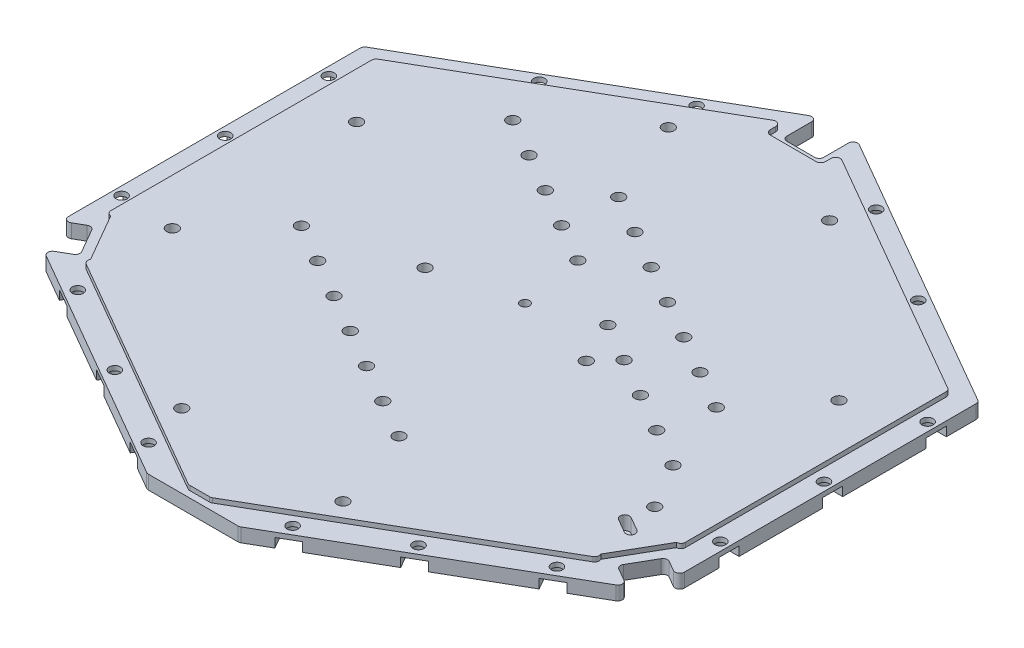
SolidWorks part; units mm, degrees
material "Copper"
ref_plane "Front Plane" through (0, 0, 0) normal (0, 0, 1) x (1, 0, 0)
ref_plane "Top Plane" through (0, 0, 0) normal (0, 1, 0) x (1, 0, 0)
ref_plane "Right Plane" through (0, 0, 0) normal (1, 0, 0) x (0, 0, -1)
sketch "Sketch1" plane through (0, 0, 0) normal (0, 1, 0) x (1, 0, 0)
  line L1 (-67.3538, -38.8868) -> (0, -77.7735)
  line L2 (0, -77.7735) -> (67.3538, -38.8868)
  line L3 (67.3538, -38.8868) -> (67.3538, 38.8868)
  line L4 (67.3538, 38.8868) -> (0, 77.7735)
  line L5 (0, 77.7735) -> (-67.3538, 38.8868)
  line L6 (-67.3538, 38.8868) -> (-67.3538, -38.8868)
  line L7 (-62.3538, -36) -> (0, -72) construction
  line L8 (0, -72) -> (62.3538, -36) construction
  line L9 (62.3538, -36) -> (62.3538, 36) construction
  line L10 (62.3538, 36) -> (0, 72) construction
  line L11 (0, 72) -> (-62.3538, 36) construction
  line L12 (-62.3538, 36) -> (-62.3538, -36) construction
  circle A0 centre (0, 0) radius 67.3538 construction
  circle A1 centre (0, 0) radius 62.3538 construction
  dimension "D1" = 5
  dimension "D2" = 72
extrude "Boss-Extrude1" add sketch "Sketch1" along normal blind 4
sketch "Sketch2" plane through (0, 4, 0) normal (0, 1, 0) x (1, 0, 0)
  line L0 (-67.3538, 38.8868) -> (-67.3538, 31.9585)
  line L1 (-67.3538, 38.8868) -> (-67.3538, -38.8868) construction
  line L2 (-67.3538, 31.9585) -> (0, 70.8453)
  line L3 (0, 70.8453) -> (67.3538, 31.9585)
  line L4 (67.3538, -38.8868) -> (67.3538, 38.8868) construction
  line L5 (67.3538, 31.9585) -> (67.3538, 38.8868)
  line L6 (67.3538, 38.8868) -> (0, 77.7735)
  line L7 (0, 77.7735) -> (-67.3538, 38.8868)
  line L8 (0, 77.7735) -> (-67.3538, 38.8868) construction
  dimension "D1" = 6
extrude "Cut-Extrude1" cut sketch "Sketch2" against normal up to next
sketch "Sketch4" plane through (0, 4, 0) normal (0, 1, 0) x (1, 0, 0)
  line L0 (-67.3538, 31.9585) -> (-67.3538, -38.8868)
  line L1 (-67.3538, 31.9585) -> (-67.3538, -38.8868) construction
  line L2 (-67.3538, -38.8868) -> (0, -77.7735)
  line L3 (0, -77.7735) -> (67.3538, -38.8868)
  line L4 (67.3538, -38.8868) -> (67.3538, 31.9585)
  line L7 (62.3538, 29.6491) -> (62.3538, -36)
  line L8 (62.3538, -36) -> (0, -72)
  line L9 (0, -72) -> (-62.3538, -36)
  line L10 (-62.3538, -36) -> (-62.3538, 29.6491)
  line L30 (-67.3538, 31.9585) -> (0, 70.8453)
  line L39 (0, 70.8453) -> (67.3538, 31.9585)
  line L40 (-62.3538, 29.6491) -> (0, 65.6491)
  line L41 (0, 65.6491) -> (62.3538, 29.6491)
  dimension "D1" = 5
  dimension "D2" = 5
  dimension "D3" = 5
  dimension "D4" = 4.5
extrude "Cut-Extrude3" cut sketch "Sketch4" against normal blind 1
sketch "Sketch8" plane through (0, 4, 0) normal (0, 1, 0) x (1, 0, 0)
  line L0 (54.3431, -31.375) -> (51.312, -29.625) construction
  line L1 (53.8431, -32.241) -> (50.812, -30.491)
  line L2 (54.8431, -30.509) -> (51.812, -28.759)
  line L4 (-62.3538, 36) -> (62.3538, -36) construction
  line L7 (62.3538, 29.6491) -> (0, 65.6491) construction
  line L8 (0, 72) -> (0, -72) construction
  circle A0 centre (0, 0) radius 1
  arc A2 (53.8431, -32.241) -> (54.8431, -30.509) centre (54.3431, -31.375) ccw
  arc A3 (51.812, -28.759) -> (50.812, -30.491) centre (51.312, -29.625) ccw
  point P6 (52.8275, -30.5)
  dimension "D1" = 2
  dimension "D2" = 1
  dimension "D3" = 3.5
  dimension "D4" = 61
extrude "Cut-Extrude5" cut sketch "Sketch8" against normal offset from surface (3 mm away) 1 up to face at (0, 0, 3.4641)
sketch "Sketch5" plane through (0, 0, 0) normal (0, -1, 0) x (1, 0, 0)
  line L0 (0, 77.7735) -> (10, 72)
  line L1 (0, 77.7735) -> (67.3538, 38.8868) construction
  line L2 (10, 72) -> (-10, 72)
  line L3 (-67.3538, 38.8868) -> (0, 77.7735) construction
  line L4 (-10, 72) -> (0, 77.7735)
  line L5 (-4, -68.5359) -> (-4, -59.8859)
  line L6 (0, -70.8453) -> (0, -59.8859) construction
  line L7 (-4, -59.8859) -> (4, -59.8859)
  line L8 (4, -59.8859) -> (4, -68.5359)
  line L9 (67.3538, 38.8868) -> (63.3538, 41.1962)
  line L10 (4, -68.5359) -> (0, -70.8453)
  line L11 (0, -70.8453) -> (-4, -68.5359)
  line L12 (0, 77.7735) -> (67.3538, 38.8868) construction
  line L13 (63.3538, 41.1962) -> (58.3049, 38.2812)
  line L14 (58.3049, 38.2812) -> (62.3049, 31.3529)
  line L15 (0, -70.8453) -> (-67.3538, -31.9585) construction
  line L16 (67.3538, -31.9585) -> (0, -70.8453) construction
  line L17 (62.3049, 31.3529) -> (67.3538, 34.2679)
  line L18 (67.3538, 38.8868) -> (67.3538, -31.9585) construction
  line L19 (67.3538, 34.2679) -> (67.3538, 38.8868)
  line L20 (-67.3538, 38.8868) -> (-67.3538, 34.2679)
  line L21 (-67.3538, -31.9585) -> (-67.3538, 38.8868) construction
  line L22 (-67.3538, 34.2679) -> (-62.3049, 31.3529)
  line L23 (-62.3049, 31.3529) -> (-58.3049, 38.2812)
  line L24 (-58.3049, 38.2812) -> (-63.3538, 41.1962)
  line L25 (-67.3538, 38.8868) -> (0, 77.7735) construction
  line L26 (-63.3538, 41.1962) -> (-67.3538, 38.8868)
  point P5 (0, 72)
  dimension "D1" = 8.65
  dimension "D2" = 8
  dimension "D3" = 120
  dimension "D4" = 5.83
  dimension "D5" = 5.83
  dimension "D6" = 8
  dimension "D7" = 8
  dimension "D8" = 4
  dimension "D9" = 4
extrude "Cut-Extrude4" cut sketch "Sketch5" against normal up to surface (3 mm away) up to face at (0, 3, 3.1754)
sketch "Sketch16" plane through (0, 0, 0) normal (0, -1, 0) x (1, 0, 0)
  line L0 (67.3538, 38.8868) -> (66.8538, 39.1754)
  line L2 (-66.8538, -31.6699) -> (-66.8538, 39.1754)
  line L4 (67.3538, -31.9585) -> (67.3538, 38.8868)
  line L5 (67.3538, 38.8868) -> (67.3538, -38.8868) construction
  line L6 (0, 77.7735) -> (67.3538, 38.8868) construction
  line L7 (-67.3538, 38.8868) -> (-66.8538, 39.1754)
  line L9 (66.8538, -31.6699) -> (66.8538, 39.1754)
  line L11 (-67.3538, -31.9585) -> (-67.3538, 38.8868)
  line L12 (-67.3538, 38.8868) -> (0, 77.7735) construction
  line L13 (-67.3538, -38.8868) -> (-67.3538, 38.8868) construction
  line L15 (66.8538, -31.6699) -> (0, -70.2679)
  line L16 (0, -70.2679) -> (-66.8538, -31.6699)
  line L18 (-67.3538, -31.9585) -> (0, -70.8453)
  line L20 (0, -70.8453) -> (67.3538, -31.9585)
  line L22 (67.3538, -31.9585) -> (4, -68.5359) construction
  line L23 (-4, -68.5359) -> (-67.3538, -31.9585) construction
  line L24 (67.3538, 34.2679) -> (67.3538, -31.9585) construction
  dimension "D1" = 0.5
  dimension "D2" = 0.5
  dimension "D3" = 0.5
  dimension "D4" = 0.5
extrude "Cut-Extrude7" cut sketch "Sketch16" against normal through all
hole_wizard "Tap Drill for M3x0.5 Tap1" positions "Sketch9" profile "Sketch10" hole size "M3x0.5" standard "ANSI Metric" end condition through all
sketch "Sketch9" plane through (0, 4, 0) normal (0, 1, 0) x (1, 0, 0)
  line L0 (-5.9392, -68.571) -> (11.3328, -38.655) construction
  line L2 (-58.3538, -38.3094) -> (0, -72) construction
  line L3 (-62.3538, -36) -> (0, -72) construction
  line L4 (-51.8644, 5.1642) -> (-35.7354, 33.1005) construction
  line L5 (-51.8644, 5.1642) -> (-18.4289, -14.1398) construction
  line L6 (-35.7354, 33.1005) -> (-2.2999, 13.7965) construction
  line L7 (-18.4289, -14.1398) -> (-2.2999, 13.7965) construction
  line L8 (-3.0309, -23.0298) -> (13.0981, 4.9065) construction
  line L9 (-3.0309, -23.0298) -> (30.4046, -42.3338) construction
  line L10 (13.0981, 4.9065) -> (46.5336, -14.3975) construction
  line L11 (30.4046, -42.3338) -> (46.5336, -14.3975) construction
  line L12 (-18.9587, 30.7468) -> (-16.9267, 34.2663) construction
  line L13 (-18.9587, 30.7468) -> (38.3216, -2.324) construction
  line L14 (-16.9267, 34.2663) -> (40.3536, 1.1956) construction
  line L15 (38.3216, -2.324) -> (40.3536, 1.1956) construction
  point P0 (11.3328, -38.655)
  point P1 (46.5336, -14.3975)
  point P3 (40.3536, 1.1956)
  point P411 (2.9739, -33.829)
  point P412 (-5.385, -29.003)
  point P413 (-13.7438, -24.177)
  point P414 (-22.1027, -19.351)
  point P415 (-30.4616, -14.525)
  point P416 (-38.8205, -9.699)
  point P431 (38.1747, -9.5715)
  point P432 (29.8158, -4.7455)
  point P433 (21.4569, 0.0805)
  point P434 (13.0981, 4.9065)
  point P437 (-2.2999, 13.7965)
  point P443 (-10.6588, 18.6225)
  point P444 (-19.0176, 23.4485)
  point P445 (-27.3765, 28.2745)
  point P446 (-35.7354, 33.1005)
  point P454 (31.9947, 6.0216)
  point P455 (23.6358, 10.8476)
  point P456 (15.2769, 15.6736)
  point P457 (6.9181, 20.4996)
  point P458 (-1.4408, 25.3256)
  point P459 (-9.7997, 30.1516)
  dimension "D1" = 34.544
  dimension "D2" = 6.858
  dimension "D3" = 7
  dimension "D4" = 32.258
  dimension "D5" = 4.064
  dimension "D6" = 32.258
  dimension "D7" = 6.35
  dimension "D8" = 6.35
  dimension "D11" = 4.826
  dimension "D12" = 7
  dimension "D13" = 8.89
  dimension "D14" = 8.89
  dimension "D9" = 5
  dimension "D10" = 5
sketch "Sketch10" plane through (11.3328, 4, 38.655) normal (1, 0, 0) x (0, 0, 1)
  line L0 (0, 0) -> (0, 4)
  line L1 (0, 4) -> (1.25, 4)
  line L2 (1.25, 4) -> (1.25, 0)
  line L5 (1.25, 0) -> (0, 0)
  line L11 (0, -6.35) -> (0, 107.95) construction
  dimension "Thru Hole Dia." = 2.5
  dimension "Thru Hole Depth" = 4
hole_wizard "Tap Drill for M3x0.5 Tap2" positions "Sketch11" profile "Sketch12" hole size "M3x0.5" standard "ANSI Metric" end condition through all
sketch "Sketch11" plane through (0, 0, 0) normal (0, -1, 0) x (-1, 0, 0)
  line L3 (17.5, -57) -> (-17.5, -57) construction
  line L4 (17.5, -57) -> (17.5, 48.637) construction
  line L5 (17.5, 48.637) -> (-17.5, 48.637) construction
  line L6 (-17.5, -57) -> (-17.5, 48.637) construction
  line L8 (52.3538, -24.1815) -> (-52.3538, -24.1815) construction
  line L9 (52.3538, -24.1815) -> (52.3538, 15.8185) construction
  line L10 (52.3538, 15.8185) -> (-52.3538, 15.8185) construction
  line L11 (-52.3538, -24.1815) -> (-52.3538, 15.8185) construction
  line L12 (-4, 59.8859) -> (4, 59.8859) construction
  line L15 (10, -72) -> (-10, -72) construction
  line L16 (0, -72) -> (0, 59.8859) construction
  line L17 (52.3538, -4.1815) -> (-52.3538, -4.1815) construction
  line L18 (-67.3538, -38.8868) -> (-67.3538, 38.8868) construction
  line L19 (67.3538, 38.8868) -> (67.3538, -38.8868) construction
  point P0 (-17.5, 48.637)
  point P2 (17.5, 48.637)
  point P8 (-52.3538, 15.8185)
  point P12 (-52.3538, -24.1815)
  point P20 (-17.5, -57)
  point P22 (17.5, -57)
  point P24 (52.3538, 15.8185)
  point P26 (52.3538, -24.1815)
  point P424 (0, 48.637)
  point P440 (17.5, -4.1815)
  point P441 (-17.5, -4.1815)
  dimension "D1" = 105.637
  dimension "D2" = 15
  dimension "D3" = 15
  dimension "D4" = 15
  dimension "D5" = 35
  dimension "D6" = 40
sketch "Sketch12" plane through (17.5, 0, -48.637) normal (1, 0, 0) x (0, 0, -1)
  line L0 (0, 0) -> (0, 4)
  line L1 (0, 4) -> (1.25, 4)
  line L2 (1.25, 4) -> (1.25, 0)
  line L5 (1.25, 0) -> (0, 0)
  line L11 (0, -6.35) -> (0, 107.95) construction
  dimension "Thru Hole Dia." = 2.5
  dimension "Thru Hole Depth" = 4
chamfer "Chamfer1" distance 2.8 1 edges at (0, 3.5, 72)
hole_wizard "CBORE for M2 SHCS2" positions "Sketch13" profile "Sketch14" counterbore size "M2" standard "ANSI Metric" end condition through all
sketch "Sketch13" plane through (0, 0, 79.328) normal (0, -1, 0) x (-1, 0, 0)
  point P0 (-65, 101.7487)
  point P1 (-41.1362, 123.5785)
  point P2 (-19.4856, 136.0785)
  point P3 (19.4856, 136.0785)
  point P4 (41.1362, 123.5785)
  point P5 (65, 101.7687)
  point P6 (65, 79.2687)
  point P7 (65, 56.7687)
  point P8 (52.0096, 34.2687)
  point P9 (32.9571, 23.2687)
  point P10 (15.6366, 13.2687)
  point P11 (-15.6366, 13.2687)
  point P12 (-32.9571, 23.2687)
  point P13 (-52.0096, 34.2687)
  point P14 (-65, 56.7487)
  point P15 (-65, 79.2487)
sketch "Sketch14" plane through (65, 0, -22.4207) normal (1, 0, 0) x (0, 0, -1)
  line L0 (0, 0) -> (0, 4)
  line L1 (0, 4) -> (1.2, 4)
  line L2 (1.2, 4) -> (1.2, 2)
  line L3 (1.2, 2) -> (2.2, 2)
  line L4 (2.2, 2) -> (2.2, 0)
  line L5 (2.2, 0) -> (0, 0)
  line L6 (0, -6.35) -> (0, 107.95) construction
  dimension "Thru Hole Dia." = 2.4
  dimension "Thru Hole Depth" = 4
  dimension "C'Bore Dia." = 4.4
  dimension "C'Bore Depth" = 2
sketch "Sketch15" plane through (0, 4, 0) normal (0, 1, 0) x (1, 0, 0)
  line L1 (6, 73.0491) -> (-6, 73.0491)
  line L2 (6, 73.0491) -> (6, 58.2491)
  line L3 (6, 58.2491) -> (-6, 58.2491)
  line L4 (-6, 73.0491) -> (-6, 58.2491)
  line L5 (6, 73.0491) -> (-6, 58.2491) construction
  line L6 (6, 58.2491) -> (-6, 73.0491) construction
  line L7 (-63.3202, -43.4862) -> (-55.3874, -38.9062)
  line L8 (-63.3202, -43.4862) -> (-69.3202, -33.0938)
  line L9 (-69.3202, -33.0938) -> (-61.3874, -28.5138)
  line L10 (-55.3874, -38.9062) -> (-61.3874, -28.5138)
  line L11 (-63.3202, -43.4862) -> (-61.3874, -28.5138) construction
  line L12 (-69.3202, -33.0938) -> (-55.3874, -38.9062) construction
  line L13 (61.3874, -28.5138) -> (69.3202, -33.0938)
  line L14 (61.3874, -28.5138) -> (55.3874, -38.9062)
  line L15 (55.3874, -38.9062) -> (63.3202, -43.4862)
  line L16 (69.3202, -33.0938) -> (63.3202, -43.4862)
  line L17 (61.3874, -28.5138) -> (63.3202, -43.4862) construction
  line L18 (55.3874, -38.9062) -> (69.3202, -33.0938) construction
  line L20 (-62.3538, -31.3812) -> (-66.8538, -33.9793) construction
  line L21 (66.8538, -33.9793) -> (62.3538, -31.3812) construction
  point P0 (0, 65.6491)
  point P6 (-62.3538, -36)
  point P12 (62.3538, -36)
  dimension "D1" = 12
  dimension "D2" = 7.4
  dimension "D3" = 12
  dimension "D4" = 12
  dimension "D5" = 4.58
  dimension "D6" = 4.58
extrude "Cut-Extrude6" cut sketch "Sketch15" against normal up to surface (1 mm away) up to face at (-52.0096, 3, 43.8593)
fillet "Fillet1" radius 1 28 edges at (4, 1.5, -59.8859) (-4, 1.5, -59.8859) (62.3538, 3.5, -29.6491) (10, 1.5, 72) (-10, 1.5, 72) (-62.3538, 3.5, -29.6491) (66.8538, 1.5, -31.6699) (-66.8538, 1.5, -31.6699) (4, 1.5, -67.9585) (-4, 1.5, -67.9585) (6, 3.5, -58.2491) (-6, 3.5, -58.2491) (6, 3.5, -62.185) (-6, 3.5, -62.185) (-2.4249, 3.5, 70.6) (2.4249, 3.5, 70.6) (58.3049, 1.5, 38.2812) (56.3538, 3.5, 39.4641) (63.3538, 1.5, 41.1962) (62.3538, 3.5, 29.0718) (66.8538, 1.5, 33.9793) (62.3049, 1.5, 31.3529) (-62.3538, 3.5, 29.0718) (-56.3538, 3.5, 39.4641) (-58.3049, 1.5, 38.2812) (-62.3049, 1.5, 31.3529) (-63.3538, 1.5, 41.1962) (-66.8538, 1.5, 33.9793)
sketch "Sketch17" plane through (0, 0, 0) normal (0, -1, 0) x (1, 0, 0)
  line L0 (-65, 24.7593) -> (-66.8538, 24.7593)
  line L1 (21.3908, -55.6505) -> (22.3726, -57.3511)
  line L2 (-65, 20.3593) -> (-66.8538, 20.3593)
  line L3 (22.3726, -57.3511) -> (18.5621, -59.5511)
  line L4 (-66.8538, 20.3593) -> (-66.8538, 24.7593)
  line L5 (18.5621, -59.5511) -> (17.5803, -57.8505)
  line L6 (21.3908, -55.6505) -> (17.5803, -57.8505) construction
  line L7 (-65, 2.2593) -> (-66.8538, 2.2593)
  line L8 (-65, -2.1407) -> (-66.8538, -2.1407)
  line L9 (-66.8538, -2.1407) -> (-66.8538, 2.2593)
  line L10 (-65, -20.2407) -> (-66.8538, -20.2407)
  line L11 (-65, -24.6407) -> (-66.8538, -24.6407)
  line L12 (-66.8538, -24.6407) -> (-66.8538, -20.2407)
  line L13 (0, -2.2) -> (0, 2.2) construction
  line L14 (66.8538, -24.6407) -> (66.8538, -20.2407)
  line L15 (65, -24.6407) -> (66.8538, -24.6407)
  line L16 (65, -20.2407) -> (66.8538, -20.2407)
  line L17 (66.8538, -2.1407) -> (66.8538, 2.2593)
  line L18 (65, -2.1407) -> (66.8538, -2.1407)
  line L19 (65, 2.2593) -> (66.8538, 2.2593)
  line L20 (66.8538, 20.3593) -> (66.8538, 24.7593)
  line L21 (65, 20.3593) -> (66.8538, 20.3593)
  line L22 (65, 24.7593) -> (66.8538, 24.7593)
  line L23 (53.9149, 43.9593) -> (50.1044, 46.1593) construction
  line L24 (10.2321, 71.866) -> (61.8538, 42.0622) construction
  line L25 (-66.8538, 23.7439) -> (-66.8538, 32.2472) construction
  line L26 (-66.8538, 1.2439) -> (-66.8538, 21.3747) construction
  line L27 (43.0415, -43.1505) -> (39.231, -45.3505) construction
  line L28 (66.3538, -31.9585) -> (42.9772, -45.4551) construction
  line L29 (43.0415, -43.1505) -> (44.0233, -44.8511)
  line L30 (44.0233, -44.8511) -> (40.2128, -47.0511)
  line L31 (41.2589, -46.4471) -> (21.3265, -57.9551) construction
  line L32 (40.2128, -47.0511) -> (39.231, -45.3505)
  line L33 (53.9149, 43.9593) -> (55.0781, 45.9741)
  line L34 (55.0781, 45.9741) -> (51.2676, 48.1741)
  line L35 (51.2676, 48.1741) -> (50.1044, 46.1593)
  line L36 (34.8623, 54.9593) -> (36.0256, 56.9741)
  line L37 (36.0256, 56.9741) -> (32.2151, 59.1741)
  line L38 (32.2151, 59.1741) -> (31.0518, 57.1593)
  line L39 (34.8623, 54.9593) -> (31.0518, 57.1593) construction
  line L40 (17.5418, 64.9593) -> (18.7051, 66.9741)
  line L41 (18.7051, 66.9741) -> (14.8946, 69.1741)
  line L42 (14.8946, 69.1741) -> (13.7313, 67.1593)
  line L43 (17.5418, 64.9593) -> (13.7313, 67.1593) construction
  line L44 (-17.5418, 64.9593) -> (-13.7313, 67.1593) construction
  line L45 (-34.8623, 54.9593) -> (-31.0518, 57.1593) construction
  line L46 (-43.0415, -43.1505) -> (-39.231, -45.3505) construction
  line L47 (-53.9149, 43.9593) -> (-50.1044, 46.1593) construction
  line L48 (-21.3908, -55.6505) -> (-17.5803, -57.8505) construction
  line L49 (-14.8946, 69.1741) -> (-13.7313, 67.1593)
  line L50 (-18.7051, 66.9741) -> (-14.8946, 69.1741)
  line L51 (-17.5418, 64.9593) -> (-18.7051, 66.9741)
  line L52 (-32.2151, 59.1741) -> (-31.0518, 57.1593)
  line L53 (-36.0256, 56.9741) -> (-32.2151, 59.1741)
  line L54 (-34.8623, 54.9593) -> (-36.0256, 56.9741)
  line L55 (-51.2676, 48.1741) -> (-50.1044, 46.1593)
  line L56 (-55.0781, 45.9741) -> (-51.2676, 48.1741)
  line L57 (-53.9149, 43.9593) -> (-55.0781, 45.9741)
  line L58 (-40.2128, -47.0511) -> (-39.231, -45.3505)
  line L59 (-44.0233, -44.8511) -> (-40.2128, -47.0511)
  line L60 (-43.0415, -43.1505) -> (-44.0233, -44.8511)
  line L61 (-18.5621, -59.5511) -> (-17.5803, -57.8505)
  line L62 (-22.3726, -57.3511) -> (-18.5621, -59.5511)
  line L63 (-21.3908, -55.6505) -> (-22.3726, -57.3511)
  arc A0 (-65, 20.3593) -> (-65, 24.7593) centre (-65, 22.5593) ccw
  arc A1 (-66.8538, 21.3747) -> (-66.8538, 23.7439) centre (-65, 22.5593) ccw construction
  arc A2 (-66.8538, 21.3747) -> (-66.8538, 23.7439) centre (-65, 22.5593) ccw construction
  arc A3 (-65, -2.1407) -> (-65, 2.2593) centre (-65, 0.0593) ccw
  arc A4 (-65, -24.6407) -> (-65, -20.2407) centre (-65, -22.4407) ccw
  arc A5 (65, -24.6407) -> (65, -20.2407) centre (65, -22.4407) cw
  arc A6 (65, -2.1407) -> (65, 2.2593) centre (65, 0.0593) cw
  arc A7 (65, 20.3593) -> (65, 24.7593) centre (65, 22.5593) cw
  arc A8 (39.231, -45.3505) -> (43.0415, -43.1505) centre (41.1362, -44.2505) cw
  arc A9 (42.9772, -45.4551) -> (41.2589, -46.4471) centre (41.1362, -44.2505) ccw construction
  arc A10 (17.5803, -57.8505) -> (21.3908, -55.6505) centre (19.4856, -56.7505) cw
  arc A11 (53.9149, 43.9593) -> (50.1044, 46.1593) centre (52.0096, 45.0593) cw
  circle A12 centre (52.0096, 45.0593) radius 2.2 construction
  arc A13 (34.8623, 54.9593) -> (31.0518, 57.1593) centre (32.9571, 56.0593) cw
  arc A14 (17.5418, 64.9593) -> (13.7313, 67.1593) centre (15.6366, 66.0593) cw
  arc A15 (-17.5418, 64.9593) -> (-13.7313, 67.1593) centre (-15.6366, 66.0593) ccw
  arc A16 (-34.8623, 54.9593) -> (-31.0518, 57.1593) centre (-32.9571, 56.0593) ccw
  arc A17 (-53.9149, 43.9593) -> (-50.1044, 46.1593) centre (-52.0096, 45.0593) ccw
  arc A18 (-17.5803, -57.8505) -> (-21.3908, -55.6505) centre (-19.4856, -56.7505) ccw
  arc A19 (-39.231, -45.3505) -> (-43.0415, -43.1505) centre (-41.1362, -44.2505) ccw
  dimension "D1" = 3
  dimension "D2" = 2
  dimension "D3" = 2
  dimension "D4" = 2
extrude "Cut-Extrude8" cut sketch "Sketch17" against normal up to surface (2 mm away) up to face at (-65, 2, -1.1407)
